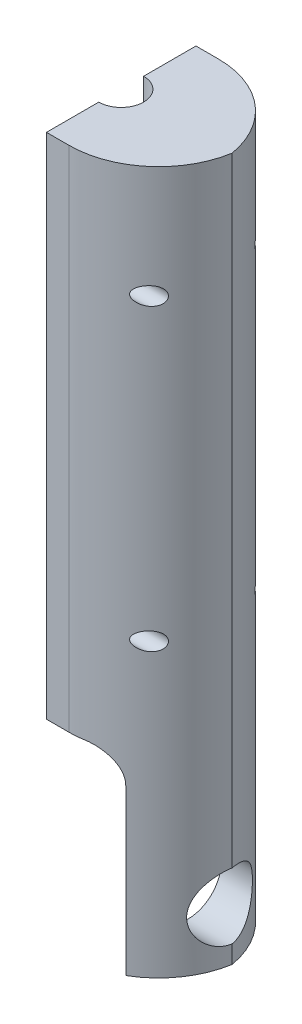
SolidWorks part; units mm, degrees
ref_plane "Plan de face" through (0, 0, 0) normal (0, 0, 1) x (1, 0, 0)
ref_plane "Plan de dessus" through (0, 0, 0) normal (0, 1, 0) x (1, 0, 0)
ref_plane "Plan de droite" through (0, 0, 0) normal (1, 0, 0) x (0, 0, -1)
sketch "Esquisse1" plane through (0, 0, 0) normal (0, 0, 1) x (1, 0, 0)
  line L0 (-129.3911, 131.107) -> (-129.3911, -98.893)
  line L1 (-129.3911, -98.893) -> (-124.3911, -98.893)
  line L2 (-124.3911, -98.893) -> (-124.3911, -33.893)
  line L3 (-124.3911, -33.893) -> (-64.3911, -33.893)
  line L4 (-64.3911, -33.893) -> (-64.3911, -98.893)
  line L5 (-64.3911, -98.893) -> (-49.3911, -98.893)
  line L6 (-49.3911, -98.893) -> (-49.3911, 131.107)
  line L7 (-49.3911, 131.107) -> (-129.3911, 131.107)
  dimension "D1" = 230
  dimension "D2" = 80
  dimension "D3" = 60
  dimension "D4" = 15
extrude "Boss.-Extru.1" add sketch "Esquisse1" along normal blind 50
fillet "Congé4" radius 35 1 edges at (-129.3911, 16.107, 50)
fillet "Congé5" radius 35 1 edges at (-129.3911, 16.107, 0)
fillet "Congé6" radius 30 2 edges at (-49.3911, 16.107, 0) (-49.3911, 16.107, 50)
fillet "Congé12" radius 10 2 edges at (-124.3911, -33.893, 21.147) (-64.3911, -33.893, 25)
sketch "Esquisse3" plane through (-64.3911, 0, 0) normal (-1, 0, 0) x (0, 0, 1)
  line L0 (25, -98.893) -> (25, -64.9421) construction
  line L1 (45.9808, -98.893) -> (4.0192, -98.893) construction
  circle A1 centre (25, -81.9176) radius 11
  dimension "D1" = 22
extrude "Enlèv. mat.-Extru.4" cut sketch "Esquisse3" against normal blind 50
sketch "Esquisse5" plane through (0, 131.107, 0) normal (0, 1, 0) x (1, 0, 0)
  line L0 (-86.8911, -50) -> (-86.8911, 0)
  line L1 (-79.3911, -50) -> (-94.3911, -50) construction
  arc A0 (-86.8911, -50) -> (-86.8911, 0) centre (-120.3634, -25) cw
extrude "Enlèv. mat.-Extru.8" cut sketch "Esquisse5" against normal blind 251
sketch "Esquisse6" plane through (-86.8911, 0, 0) normal (-1, 0, 0) x (0, 0, 1)
  line L0 (25, 131.107) -> (25, -33.893) construction
  line L1 (50, 131.107) -> (0, 131.107) construction
  line L2 (50, -33.893) -> (0, -33.893) construction
  line L4 (50, -33.893) -> (50, 131.107) construction
  line L5 (50, 48.607) -> (0, 48.607) construction
  line L6 (0, -33.893) -> (0, 131.107) construction
  circle A0 centre (7.5, 98.607) radius 2
  circle A1 centre (42.5, 98.607) radius 2
  circle A2 centre (42.5, -1.393) radius 2
  circle A3 centre (7.5, -1.393) radius 2
  dimension "D1" = 35
  dimension "D2" = 50
extrude "Enlèv. mat.-Extru.9" cut sketch "Esquisse6" against normal blind 58
sketch "Esquisse9" plane through (0, 131.107, 0) normal (0, 1, 0) x (1, 0, 0)
  line L0 (-86.8911, -50) -> (-86.8911, 0) construction
  line L1 (-49.8107, -25) -> (-86.8911, -25) construction
  arc A0 (-86.8911, -17.5) -> (-86.8911, -32.5) centre (-86.8911, -25) cw
  point P8 (-94.3911, -25)
  point P9 (0, 0)
  dimension "D1" = 15
extrude "Enlèv. mat.-Extru.12" cut sketch "Esquisse9" against normal blind 179 and the other way through all flip side to cut
ref_plane "Plan2" through (-49.8107, 0, 0) normal (-1, 0, 0) x (0, 0, 1)
sketch "Esquisse11" plane through (-49.8107, 0, 0) normal (-1, 0, 0) x (0, 0, 1)
  circle A8 centre (42.5, 98.607) radius 3
  circle A9 centre (7.5, 98.607) radius 3
  circle A10 centre (42.5, -1.393) radius 3
  circle A11 centre (7.5, -1.393) radius 3
extrude "Enlèv. mat.-Extru.14" cut sketch "Esquisse11" along normal blind 20
sketch "Esquisse12" plane through (0, 131.107, 0) normal (0, 1, 0) x (1, 0, 0)
  line L0 (-79.3911, 0) -> (-86.8911, 0) construction
  line L1 (-86.8911, -17.5) -> (-86.8911, 0) construction
  line L2 (-86.8911, -50) -> (-86.8911, -32.5) construction
  line L3 (-79.3911, -50) -> (-86.8911, -50) construction
  line L4 (-79.3911, 0) -> (-86.8911, 0)
  line L5 (-86.8911, -17.5) -> (-86.8911, 0)
  line L6 (-86.8911, -50) -> (-86.8911, -32.5)
  line L7 (-79.3911, -50) -> (-86.8911, -50)
  arc A0 (-86.8911, -32.5) -> (-86.8911, -17.5) centre (-86.8911, -25) ccw construction
  arc A1 (-79.3911, -50) -> (-49.8107, -25) centre (-79.3911, -20) ccw construction
  arc A2 (-49.8107, -25) -> (-79.3911, 0) centre (-79.3911, -30) ccw construction
  arc A3 (-86.8911, -32.5) -> (-86.8911, -17.5) centre (-86.8911, -25) ccw
  arc A4 (-79.3911, -50) -> (-49.8107, -25) centre (-79.3911, -20) ccw
  arc A5 (-49.8107, -25) -> (-79.3911, 0) centre (-79.3911, -30) ccw
extrude "Boss.-Extru.2" add sketch "Esquisse12" along normal blind 5
